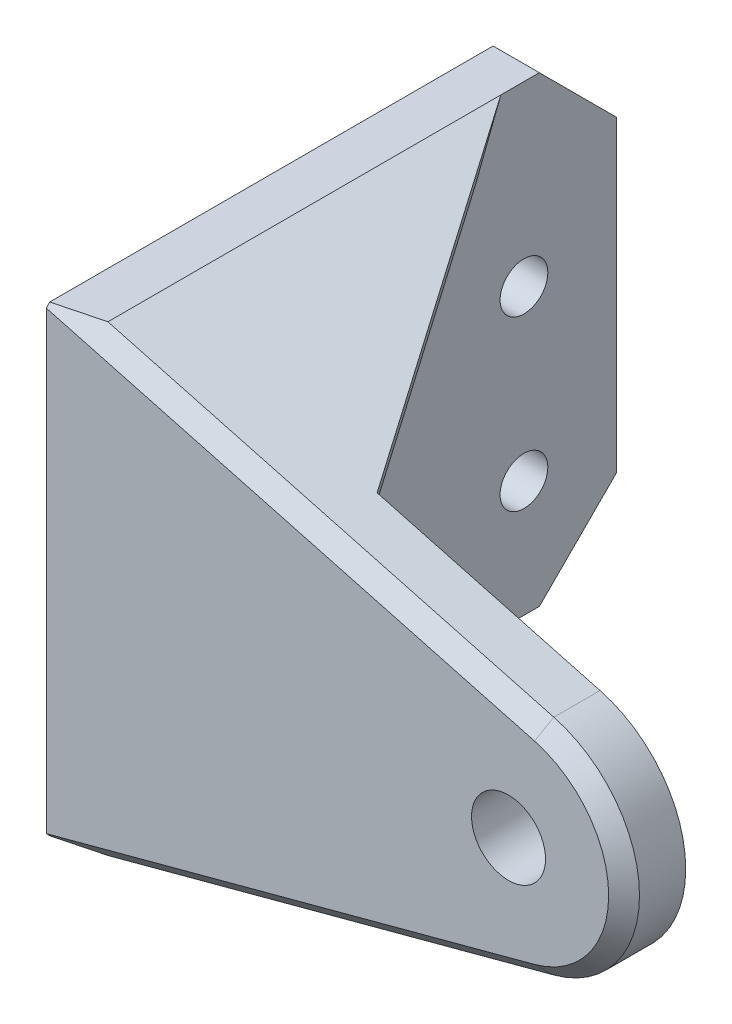
SolidWorks part; units mm, degrees
ref_plane "Front Plane" through (0, 0, 0) normal (0, 0, 1) x (1, 0, 0)
ref_plane "Top Plane" through (0, 0, 0) normal (0, 1, 0) x (1, 0, 0)
ref_plane "Right Plane" through (0, 0, 0) normal (1, 0, 0) x (0, 0, -1)
sketch "Sketch1" plane through (0, 0, 0) normal (0, 0, 1) x (1, 0, 0)
  line L0 (-24.444, 5.5562) -> (-24.444, -9.4438)
  line L1 (5.556, 5.5562) -> (-24.444, 5.5562) construction
  line L2 (-24.444, 5.5562) -> (-24.444, 20.5562)
  line L3 (-24.444, -9.4438) -> (-21.444, -9.4438)
  line L4 (-21.444, -9.4438) -> (7.4973, -1.6881)
  line L5 (-24.444, 20.5562) -> (-21.444, 20.5562)
  line L6 (-21.444, 20.5562) -> (7.4973, 12.8006)
  circle A1 centre (5.556, 5.5562) radius 1.984
  circle A2 centre (5.556, 5.5562) radius 7.5
  dimension "D1" = 15
  dimension "D2" = 30
  dimension "D3" = 15
  dimension "D4" = 15
  dimension "D5" = 3
  dimension "D6" = 3
extrude "Boss-Extrude1" add sketch "Sketch1" along normal blind 4 contours A2 L1 L0 L3 L4 | L1 A2 L6 L5 L2 | A1 A2 | A1 region at (-13.0294, -0.9504, 0) region at (-13.0294, 12.0629, 0) region at (5.556, 7.4841, 0) region at (1.1195, 11.3382, 0)
sketch "Sketch2" plane through (0, 0, 4) normal (0, 0, 1) x (1, 0, 0)
  circle A0 centre (5.556, 5.5562) radius 1.984 construction
  circle A1 centre (5.556, 5.5562) radius 1.984
  circle A2 centre (5.556, 5.5562) radius 1.05
  dimension "D1" = 2.1
sketch "Sketch3" plane through (0, 0, 0) normal (0, 0, -1) x (-1, 0, 0)
  line L0 (21.444, 20.5562) -> (21.444, -9.4438)
  line L1 (21.444, -9.4438) -> (24.444, -9.4438)
  line L2 (24.444, -9.4438) -> (24.444, 20.5562)
  line L3 (24.444, 20.5562) -> (21.444, 20.5562)
extrude "Boss-Extrude2" add sketch "Sketch3" along normal blind 30
sketch "Sketch4" plane through (3.7028, 13.8175, 0) normal (0.2588, 0.9659, 0) x (0.9659, -0.2588, 0)
  line L0 (-26.034, 22.5) -> (-11.0528, 0)
  line L1 (-26.034, 0) -> (3.9284, 0) construction
  line L3 (-26.034, 15) -> (-26.034, 30) construction
  line L4 (-26.034, 30) -> (-26.034, 0) construction
  line L5 (-11.0528, 0) -> (-11.0528, -0.5)
  line L6 (-11.0528, -0.5) -> (-26.034, -0.5)
  line L7 (-26.034, -4) -> (-26.034, 0) construction
  line L8 (-26.034, -0.5) -> (-26.034, 22.5)
  dimension "D1" = 0.5
extrude "Boss-Extrude3" add sketch "Sketch4" against normal blind 4
ref_axis "Axis1" through (5.556, 5.5562, 0) along (-1, 0, 0)
ref_plane "Plane1" through (0, 5.5562, 0) normal (0, 1, 0) x (-1, 0, 0)
chamfer "Chamfer1" distance 5 angle 45 1 edges at (-21.444, 3.4857, 0)
chamfer "Chamfer2" distance 5 angle 45 2 edges at (-22.944, -9.4438, -30) (-22.944, 20.5562, -30)
chamfer "Chamfer3" distance 1 angle 45 3 edges at (-6.9733, -5.5659, 4) (13.056, 5.5562, 4) (-6.9733, 16.6784, 4)
sketch "Sketch6" plane through (-21.444, 0, 0) normal (1, 0, 0) x (0, 0, -1)
  line L0 (30, 9.0472) -> (9.61, 9.0472) construction
  line L1 (30, 15.5562) -> (30, -4.4438) construction
  line L2 (30, -1.8898) -> (9.5502, -1.8898) construction
  line L3 (24, 9.0472) -> (24, -1.8898) construction
  line L4 (11, 9.0472) -> (11, -1.8898) construction
  circle A0 centre (11, 9.0472) radius 1.55
  circle A1 centre (24, 9.0472) radius 1.55
  circle A2 centre (11, -1.8898) radius 1.55
  circle A3 centre (24, -1.8898) radius 1.55
  dimension "D1" = 3.1
  dimension "D2" = 3.1
  dimension "D3" = 3.1
  dimension "D4" = 3.1
  dimension "D5" = 6
  dimension "D6" = 13
extrude "Cut-Extrude3" cut sketch "Sketch6" against normal up to next
sketch "Sketch7" plane through (0, 0, 0) normal (0, 0, -1) x (-1, 0, 0)
  circle A0 centre (-5.556, 5.5562) radius 1.05 construction
  circle A1 centre (-5.556, 5.5562) radius 1.05
  circle A2 centre (-5.556, 5.5562) radius 2.4
  dimension "D1" = 4.8
ref_point "Point1"
extrude "Cut-Extrude4" cut sketch "Sketch7" against normal up to next contours A2
